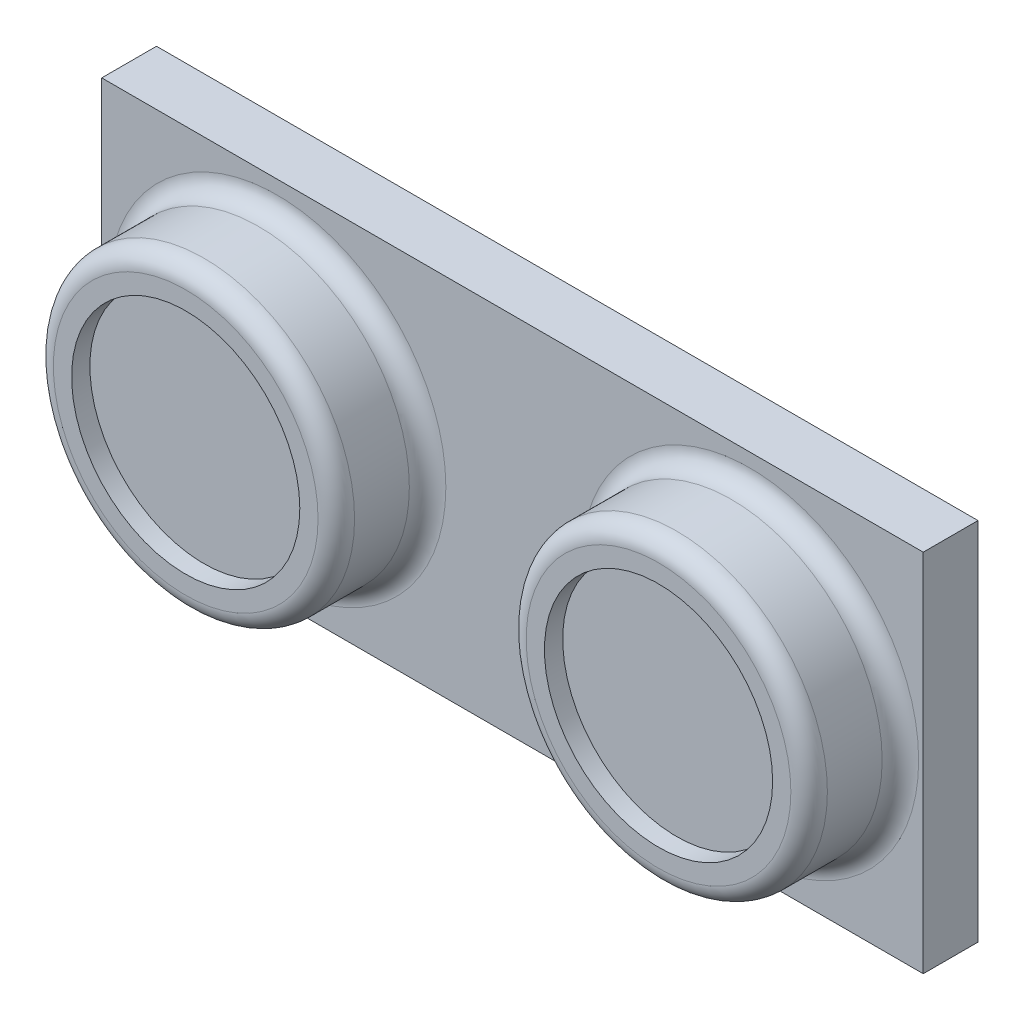
SolidWorks part; units mm, degrees
ref_plane "前视基准面" through (0, 0, 0) normal (0, 0, 1) x (1, 0, 0)
ref_plane "上视基准面" through (0, 0, 0) normal (0, 1, 0) x (1, 0, 0)
ref_plane "右视基准面" through (0, 0, 0) normal (1, 0, 0) x (0, 0, -1)
sketch "草图1" plane through (0, 0, 0) normal (0, 0, 1) x (1, 0, 0)
  line L1 (-22.5, -10) -> (22.5, -10)
  line L2 (-22.5, -10) -> (-22.5, 10)
  line L3 (-22.5, 10) -> (22.5, 10)
  line L4 (22.5, -10) -> (22.5, 10)
  line L5 (-22.5, -10) -> (22.5, 10) construction
  line L6 (-22.5, 10) -> (22.5, -10) construction
  circle A0 centre (-12.9, 0) radius 8.25
  circle A1 centre (13, 0) radius 8.25
  point P0 (0, 0)
  point P10 (0, 0)
  point P11 (0, 0)
  point P12 (9.8243, 0)
  dimension "D3" = 16.5
  dimension "D1" = 20
  dimension "D2" = 45
  dimension "D4" = 25.9
  dimension "D5" = 13
extrude "凸台-拉伸1" add sketch "草图1" along normal blind 3 contours A0 | A1 | L1 L4 L3 L2 A1 A0 region at (-0.0453, 0, 0) region at (-12.9, 0, 0) region at (13, 0, 0)
extrude "凸台-拉伸2" add sketch "草图1<3>" along normal blind 8 contours A0 | A1 region at (-12.9, 0, 0) region at (13, 0, 0)
sketch "草图1<3>" plane through (0, 0, 0) normal (0, 0, 1) x (1, 0, 0) same geometry as "草图1"
sketch "草图2" plane through (0, 0, 8) normal (0, 0, 1) x (1, 0, 0)
  circle A0 centre (13, 0) radius 8.25 construction
  circle A1 centre (-12.9, 0) radius 8.25 construction
  circle A2 centre (13, 0) radius 8.25 construction
  circle A3 centre (-12.9, 0) radius 8.25 construction
  circle A4 centre (13, 0) radius 6.25
  circle A5 centre (-12.9, 0) radius 6.25
  dimension "D1" = 2
extrude "切除-拉伸1" cut sketch "草图2" against normal blind 1
fillet "圆角1" radius 1 4 edges at (21.25, 0, 8) (21.25, 0, 3) (-4.65, 0, 8) (-4.65, 0, 3)
